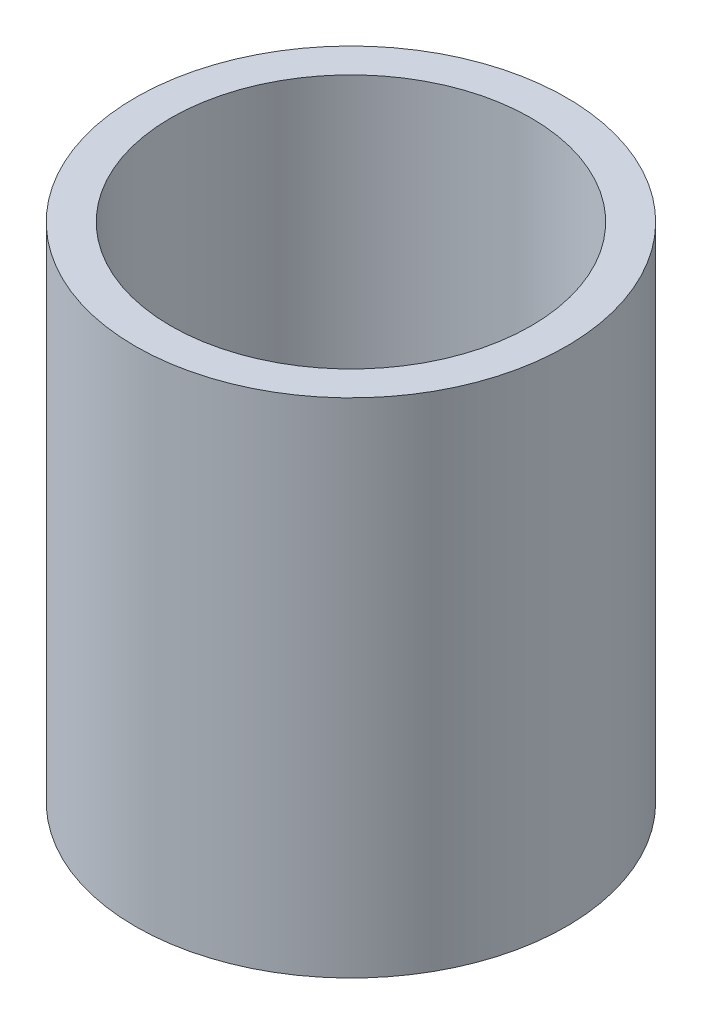
SolidWorks part; units mm, degrees
ref_plane "Front Plane" through (0, 0, 0) normal (0, 0, 1) x (1, 0, 0)
ref_plane "Top Plane" through (0, 0, 0) normal (0, 1, 0) x (1, 0, 0)
ref_plane "Right Plane" through (0, 0, 0) normal (1, 0, 0) x (0, 0, -1)
sketch "Sketch1" plane through (0, 0, 0) normal (0, 1, 0) x (1, 0, 0)
  circle A0 centre (0, 0) radius 20
  dimension "SLEEVE_OD" = 40
extrude "Boss-Extrude1" add sketch "Sketch1" along normal blind 46.6354
sketch "Sketch2" plane through (0, 0, 0) normal (0, 1, 0) x (1, 0, 0)
  circle A0 centre (0, 0) radius 16.7196
  dimension "BORE_D" = 33.4392
extrude "Cut-Extrude1" cut sketch "Sketch2" along normal through all
chamfer "Chamfer1" distance 2.9034 angle 24.154 rebuild error yes
